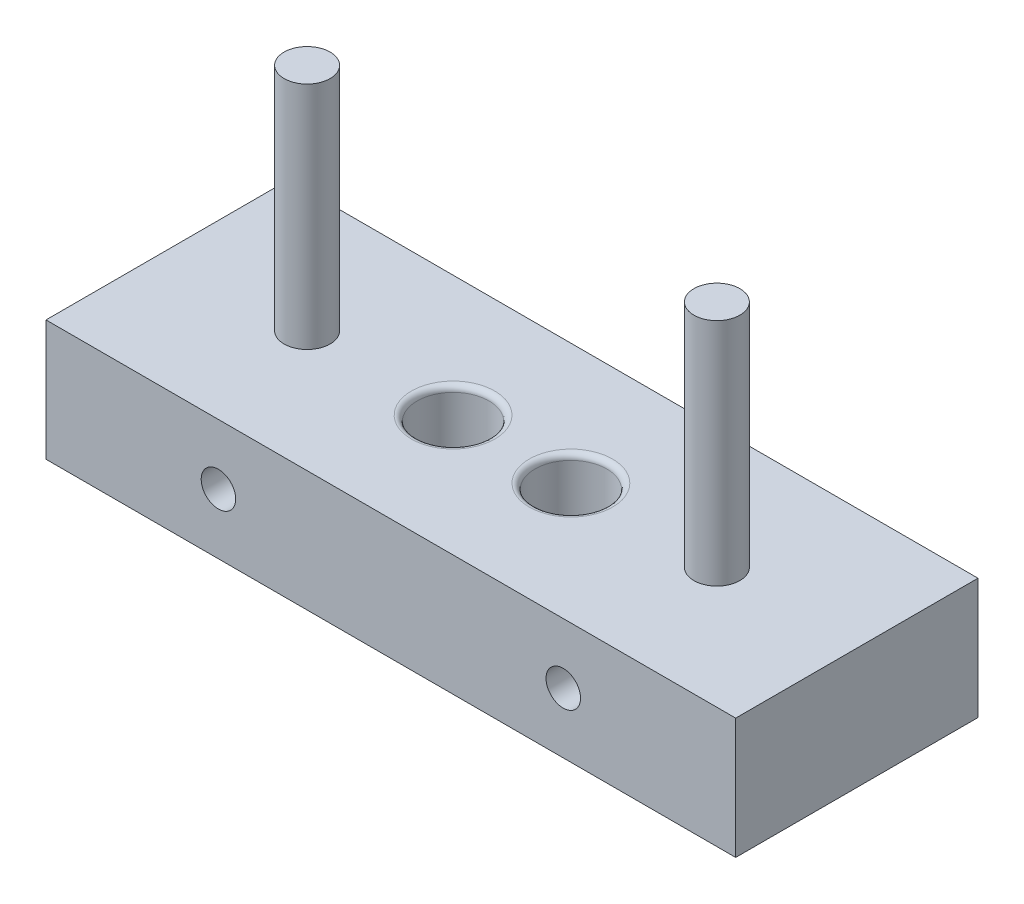
SolidWorks part; units mm, degrees
ref_plane "Front Plane" through (0, 0, 0) normal (0, 0, 1) x (1, 0, 0)
ref_plane "Top Plane" through (0, 0, 0) normal (0, 1, 0) x (1, 0, 0)
ref_plane "Right Plane" through (0, 0, 0) normal (1, 0, 0) x (0, 0, -1)
sketch "Sketch1" plane through (0, 0, 0) normal (0, 1, 0) x (1, 0, 0)
  line L1 (-43.189, 20.5655) -> (76.811, 20.5655)
  line L2 (-43.189, 20.5655) -> (-43.189, -21.5945)
  line L3 (-43.189, -21.5945) -> (76.811, -21.5945)
  line L4 (76.811, 20.5655) -> (76.811, -21.5945)
  dimension "D1" = 42.16
  dimension "D2" = 120
extrude "Boss-Extrude1" add sketch "Sketch1" along normal blind 21
sketch "Sketch2" plane through (0, 21, 0) normal (0, 1, 0) x (1, 0, 0)
  line L0 (-43.189, -0.5145) -> (76.811, -0.5145) construction
  line L1 (16.811, -21.5945) -> (16.811, 20.5655) construction
  line L2 (27.061, -21.5945) -> (27.061, 20.5655)
  line L3 (6.561, -21.5945) -> (6.561, 20.5655)
  line L4 (-43.189, 20.5655) -> (-43.189, -21.5945)
  line L5 (-43.189, -21.5945) -> (76.811, -21.5945)
  line L6 (76.811, -21.5945) -> (76.811, 20.5655)
  line L7 (76.811, 20.5655) -> (-43.189, 20.5655)
  line L8 (-43.189, 20.5655) -> (-43.189, -21.5945)
  line L9 (-43.189, -21.5945) -> (76.811, -21.5945)
  line L10 (76.811, -21.5945) -> (76.811, 20.5655)
  line L11 (76.811, 20.5655) -> (-43.189, 20.5655)
  circle A0 centre (27.061, -0.5145) radius 6.25
  circle A1 centre (6.561, -0.5145) radius 6.25
  dimension "D1" = 0
  dimension "D2" = 21.08
  dimension "D3" = 60
  dimension "D4" = 10.25
  dimension "D5" = 10.25
extrude "Cut-Extrude1" cut sketch "Sketch2" against normal blind 14 contours L2 A0 | L2 A0 | L3 A1 | L3 A1 region at (24.4084, 21, 0.5145) region at (29.7136, 21, 0.5145) region at (3.9084, 21, 0.5145) region at (9.2136, 21, 0.5145)
sketch "Sketch3" plane through (0, 7, 0) normal (0, 1, 0) x (1, 0, 0)
  circle A4 centre (27.061, -0.5145) radius 3.25
  circle A5 centre (6.561, -0.5145) radius 3.25
extrude "Cut-Extrude2" cut sketch "Sketch3" against normal through all
fillet "Fillet1" radius 1 2 edges at (6.561, 21, 6.7645) (27.061, 21, 6.7645)
fillet "Fillet2" radius 0.5 2 edges at (6.561, 0, 3.7645) (27.061, 0, 3.7645)
sketch "Sketch4" plane through (0, 21, 0) normal (0, 1, 0) x (1, 0, 0)
  line L0 (6.561, -0.5145) -> (27.061, -0.5145) construction
  line L1 (76.811, 20.5655) -> (-43.189, 20.5655) construction
  line L2 (-43.189, -21.5945) -> (76.811, -21.5945) construction
  line L3 (52.461, -21.5945) -> (52.461, 20.5655)
  line L6 (-18.839, -21.5945) -> (-18.839, 20.5655)
  circle A0 centre (52.461, -0.5145) radius 4
  circle A1 centre (-18.839, -0.5145) radius 4
  point P12 (16.811, -0.5145)
  dimension "D4" = 8
  dimension "D1" = 71.3
  dimension "D2" = 35.65
extrude "Boss-Extrude2" add sketch "Sketch4" along normal blind 40 contours L3 A0 | L3 A0 | L6 A1 | L6 A1 region at (50.7634, 21, 0.5145) region at (54.1587, 21, 0.5145) region at (-20.5366, 21, 0.5145) region at (-17.1413, 21, 0.5145)
sketch "Sketch5" plane through (0, 21, 0) normal (0, 1, 0) x (1, 0, 0)
  circle A1 centre (52.461, -0.5145) radius 4 construction
  circle A3 centre (52.461, -0.5145) radius 4
curve "Helix/Spiral1" [suppressed] pitch 0.75 height 54 turns 72
sketch "Sketch6" plane through (0, 61, 0) normal (0, 1, 0) x (1, 0, 0)
  circle A1 centre (52.461, -0.5145) radius 4
  circle A2 centre (52.461, -0.5145) radius 4
  dimension "D1" = 0
ref_plane "Plane1" through (0, 0, 0.5145) normal (0, 0, 1) x (1, 0, 0)
sketch "Sketch18" plane through (0, 0, 0.5145) normal (0, 0, 1) x (1, 0, 0)
  line L3 (-43.189, 21) -> (76.811, 21) construction
  line L4 (59.811, 21) -> (60.561, 21)
  line L7 (59.811, 21) -> (60.561, 20.5)
  line L8 (60.561, 20.5) -> (60.561, 21)
  dimension "D1" = 0.75
  dimension "D2" = 0.5
sweep "Cut-Sweep3" [suppressed] cut profiles "Sketch18" path "Helix/Spiral1"
ref_plane "Plane2" through (16.811, 0, 0) normal (-1, 0, 0) x (0, 0, -1)
mirror "Mirror1" [suppressed] about plane through (16.811, 0, 0) normal (-1, 0, 0)
sketch "Sketch19" plane through (0, 0, -20.5655) normal (0, 0, -1) x (-1, 0, 0)
  line L1 (43.189, 21) -> (43.189, 0) construction
  line L2 (-76.811, 21) -> (-76.811, 0) construction
  circle A1 centre (13.189, 10.5) radius 3
  circle A2 centre (-46.811, 10.5) radius 3
  dimension "D1" = 6
  dimension "D2" = 6
  dimension "D3" = 30
  dimension "D4" = 30
extrude "Cut-Extrude3" cut sketch "Sketch19" against normal through all
